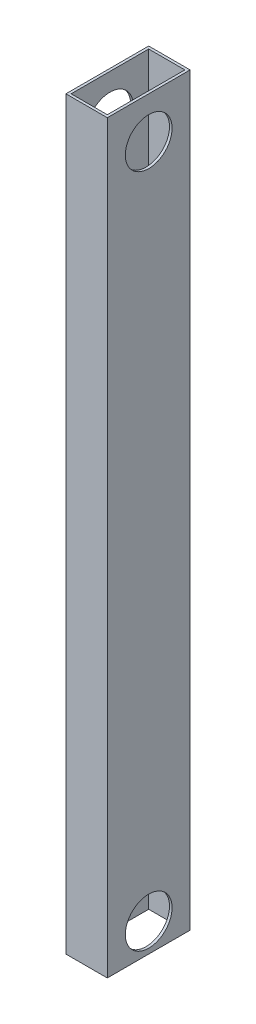
SolidWorks part; units mm, degrees
ref_plane "Front Plane" through (0, 0, 0) normal (0, 0, 1) x (1, 0, 0)
ref_plane "Top Plane" through (0, 0, 0) normal (0, 1, 0) x (1, 0, 0)
ref_plane "Right Plane" through (0, 0, 0) normal (1, 0, 0) x (0, 0, -1)
sketch "Sketch1" plane through (0, 0, 0) normal (0, 1, 0) x (1, 0, 0)
  line L1 (0, 0) -> (25.4, 0)
  line L2 (0, 0) -> (0, 50.8)
  line L3 (0, 50.8) -> (25.4, 50.8)
  line L4 (25.4, 0) -> (25.4, 50.8)
  dimension "D1" = 50.8
  dimension "D2" = 25.4
extrude "Extrude-Thin1" add sketch "Sketch1" along normal blind 457.2 thin thin type one direction reverse wall 1.5875
sketch "Sketch2" plane through (25.4, 0, 0) normal (1, 0, 0) x (0, 0, -1)
  line L0 (0, 0) -> (50.8, 0) construction
  line L1 (0, 457.2) -> (0, 0) construction
  line L2 (0, 457.2) -> (50.8, 457.2) construction
  circle A0 centre (25.4, 17.526) radius 14.351
  circle A1 centre (25.4, 431.8) radius 14.351
  dimension "D1" = 17.526
  dimension "D2" = 28.702
  dimension "D4" = 25.4
  dimension "D5" = 28.702
  dimension "D6" = 25.4
  dimension "D3" = 25.4
extrude "Cut-Extrude1" cut sketch "Sketch2" against normal through all both and the other way through all
